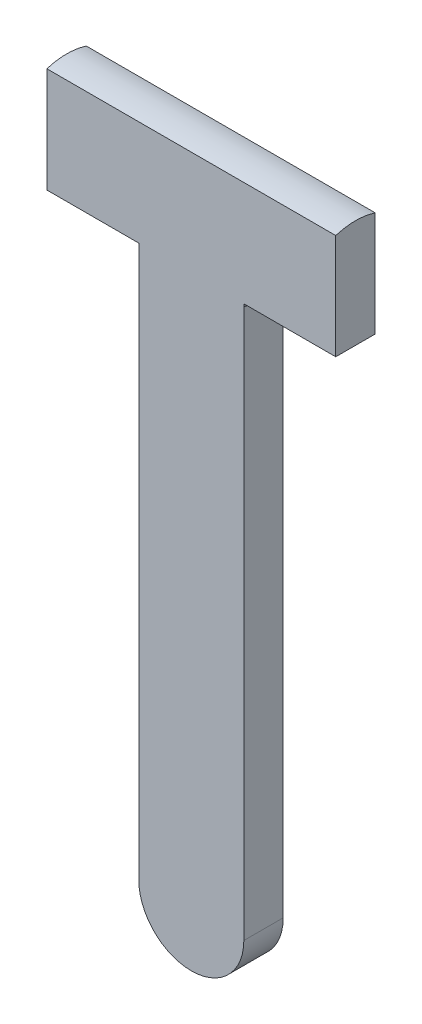
SolidWorks part; units mm, degrees
ref_plane "Face" through (0, 0, 0) normal (0, 0, 1) x (1, 0, 0)
ref_plane "Dessus" through (0, 0, 0) normal (0, 1, 0) x (1, 0, 0)
ref_plane "Droite" through (0, 0, 0) normal (1, 0, 0) x (0, 0, -1)
sketch "Esquisse1" plane through (0, 0, 0) normal (0, 0, 1) x (1, 0, 0)
  line L0 (-5.5, 0) -> (5.5, 0)
  line L1 (-5.5, -4) -> (-2, -4)
  line L2 (0, 0) -> (0, -33.6958) construction
  line L3 (-5.5, 0) -> (-5.5, -4)
  line L5 (5.5, -4) -> (5.5, 0)
  line L6 (2, -4) -> (5.5, -4)
  line L8 (-2, -4) -> (-2, -25)
  line L10 (2, -4) -> (2, -25)
  arc A0 (-2, -25) -> (2, -25) centre (0, -25) ccw
  dimension "D5" = 25
  dimension "D1" = 4
  dimension "D2" = 11
  dimension "D3" = 4
  dimension "D4" = 3.5
  dimension "D6" = 11
extrude "Extrusion1" add sketch "Esquisse1" along normal blind 1.5
sketch "Esquisse2" plane through (0, -4, 0) normal (0, -1, 0) x (1, 0, 0)
  line L1 (-2, 1.5) -> (-2, 0) construction
  line L3 (-2, 1.5) -> (-2, 0)
  line L4 (2, 1.5) -> (2, 0) construction
  line L5 (2, 1.5) -> (2, 0)
  arc A0 (-2, 1.5) -> (-2, 0) centre (0, 0.75) ccw
  arc A1 (2, 0) -> (2, 1.5) centre (0, 0.75) ccw
extrude "Extrusion2" add sketch "Esquisse2" along normal blind 0.1
sketch "Esquisse3" plane through (-5.5, 0, 0) normal (-1, 0, 0) x (0, 0, 1)
  line L0 (1.5, 0) -> (0, 0) construction
  line L1 (1.5, 0) -> (0, 0)
  arc A0 (1.5, 0) -> (0, 0) centre (0.75, -2.3848) ccw
  dimension "D1" = 5
extrude "Extrusion3" add sketch "Esquisse3" against normal up to surface (11 mm away) up to face at (5.5, -2, 0.75)
ref_axis "Axe1" through (0, 0, 0) along (0, -1, 0)
